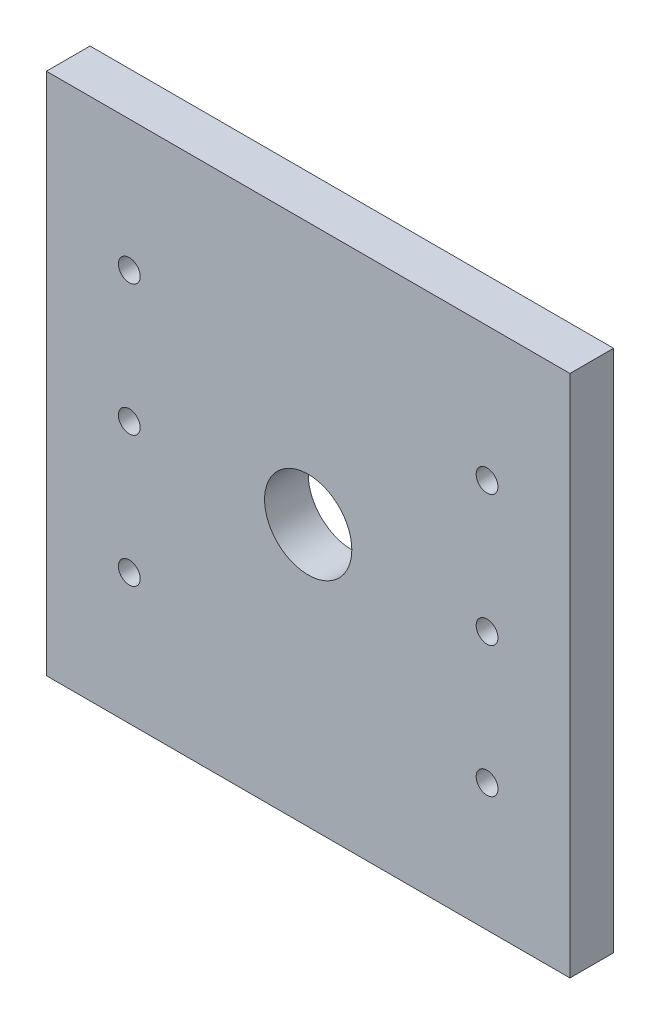
SolidWorks part; units mm, degrees
ref_plane "Front Plane" through (0, 0, 0) normal (0, 0, 1) x (1, 0, 0)
ref_plane "Top Plane" through (0, 0, 0) normal (0, 1, 0) x (1, 0, 0)
ref_plane "Right Plane" through (0, 0, 0) normal (1, 0, 0) x (0, 0, -1)
sketch "Sketch1" plane through (0, 0, 0) normal (0, 1, 0) x (1, 0, 0)
  line L1 (-60, -5) -> (60, -5)
  line L2 (-60, -5) -> (-60, 5)
  line L3 (-60, 5) -> (60, 5)
  line L4 (60, -5) -> (60, 5)
  line L5 (-60, -5) -> (60, 5) construction
  line L6 (-60, 5) -> (60, -5) construction
  point P0 (0, 0)
  dimension "D1" = 120
  dimension "D2" = 10
extrude "Boss-Extrude1" add sketch "Sketch1" along normal blind 120
sketch "Sketch2" plane through (0, 0, 5) normal (0, 0, 1) x (1, 0, 0)
  circle A0 centre (0, 60) radius 10
  circle A1 centre (-41, 60) radius 2.5
  circle A2 centre (-41, 30) radius 2.5
  circle A3 centre (-41, 90) radius 2.5
  circle A4 centre (41, 59.255) radius 2.5
  circle A5 centre (41, 29.255) radius 2.5
  circle A6 centre (41, 89.255) radius 2.5
  point P0 (0, 0)
  point P1 (0, 60)
  point P18 (0, 0)
  dimension "D3" = 41
  dimension "D4" = 30
  dimension "D1" = 60
  dimension "D2" = 60
  dimension "D5" = 30
  dimension "D6" = 41
  dimension "D7" = 30
  dimension "D8" = 30
extrude "Cut-Extrude1" cut sketch "Sketch2" against normal up to surface (10 mm away) up to face at (0, 60, -5)
